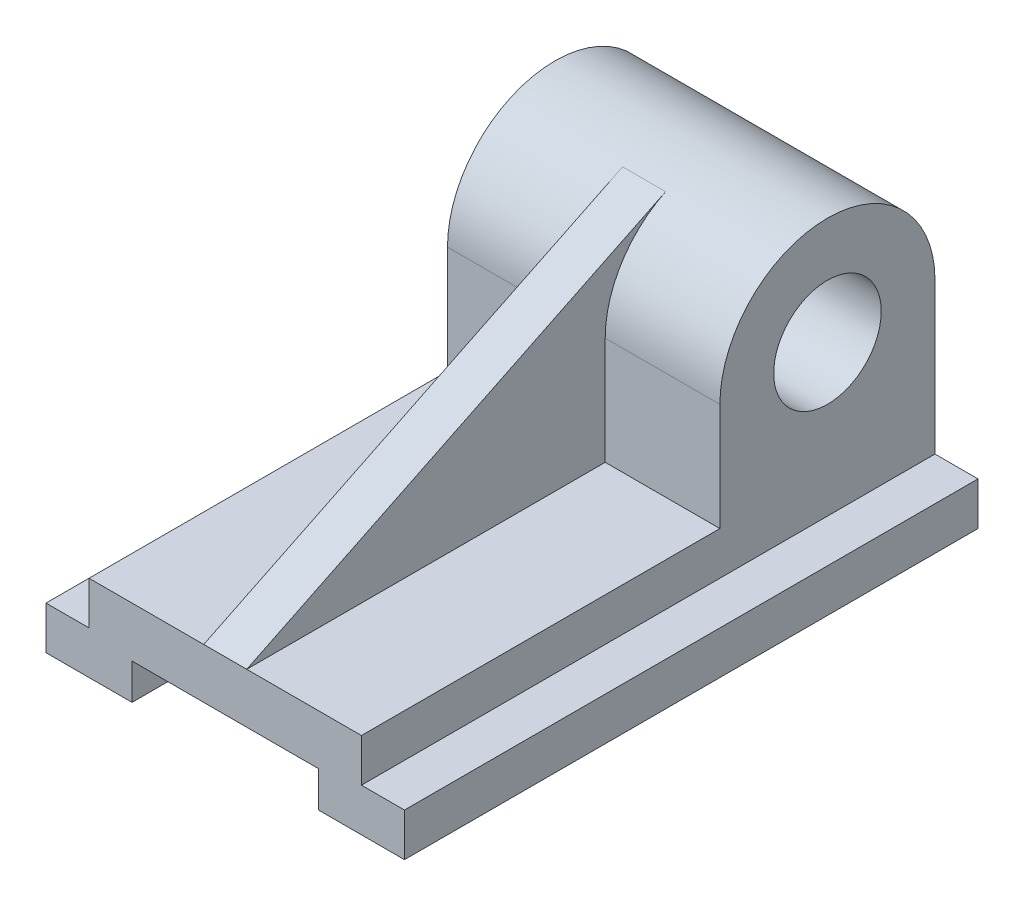
SolidWorks part; units mm, degrees
ref_plane "Front Plane" through (0, 0, 0) normal (0, 0, 1) x (1, 0, 0)
ref_plane "Top Plane" through (0, 0, 0) normal (0, 1, 0) x (1, 0, 0)
ref_plane "Right Plane" through (0, 0, 0) normal (1, 0, 0) x (0, 0, -1)
sketch "Sketch1" plane through (0, 0, 0) normal (0, 0, 1) x (1, 0, 0)
  line L1 (-50, 12) -> (50, 12)
  line L2 (-50, 12) -> (-50, -12)
  line L3 (-50, -12) -> (50, -12)
  line L4 (50, 12) -> (50, -12)
  line L5 (-50, 12) -> (50, -12) construction
  line L6 (-50, -12) -> (50, 12) construction
  point P0 (0, 0)
  dimension "D1" = 100
  dimension "D2" = 24
extrude "Boss-Extrude1" add sketch "Sketch1" along normal blind 160
sketch "Sketch2" plane through (0, 0, 160) normal (0, 0, 1) x (1, 0, 0)
  line L0 (-50, -12) -> (50, -12) construction
  line L1 (-26, -12) -> (26, -12)
  line L2 (-26, -12) -> (-26, -2)
  line L3 (-26, -2) -> (26, -2)
  line L4 (26, -12) -> (26, -2)
  line L6 (50, -12) -> (50, 12) construction
  dimension "D1" = 10
  dimension "D2" = 52
  dimension "D3" = 24
extrude "Cut-Extrude1" cut sketch "Sketch2" against normal through all
sketch "Sketch3" plane through (0, 0, 160) normal (0, 0, 1) x (1, 0, 0)
  line L1 (50, 12) -> (38, 12)
  line L2 (50, 12) -> (50, 0)
  line L3 (50, 0) -> (38, 0)
  line L4 (38, 12) -> (38, 0)
  dimension "D1" = 12
  dimension "D2" = 12
extrude "Cut-Extrude2" cut sketch "Sketch3" against normal through all contours L4 L3 L2 L1
mirror "Mirror1" about plane through (0, 0, 0) normal (1, 0, 0) of "Cut-Extrude2"
sketch "Sketch4" plane through (0, 12, 0) normal (0, 1, 0) x (1, 0, 0)
  line L0 (38, 0) -> (38, -160) construction
  line L1 (-38, 0) -> (38, 0)
  line L2 (-38, 0) -> (-38, -60)
  line L3 (-38, -60) -> (38, -60)
  line L4 (38, 0) -> (38, -60)
  dimension "D1" = 60
extrude "Boss-Extrude3" add sketch "Sketch4" along normal blind 60 contours L3 L4 L1 L2
fillet "Fillet2" 2 edges at (0, 72, 60) (0, 72, 0) type full round first side face at (0, 42, 60) second side face at (0, 7.6667, 0) middle face at (0, 72, 30)
sketch "Sketch6" plane through (38, 0, 0) normal (1, 0, 0) x (0, 0, -1)
  circle A0 centre (-30, 42) radius 15
  dimension "D1" = 30
extrude "Cut-Extrude3" cut sketch "Sketch6" against normal through all
sketch "Sketch9" plane through (0, 0, 0) normal (1, 0, 0) x (0, 0, -1)
  line L0 (-160, 12) -> (-43.1461, 68.9663)
  arc A0 (0, 42) -> (-60, 42) centre (-30, 42) ccw construction
rib "Rib3" sketch "Sketch9" sketch "Sketch9" thickness 12 extrusion direction parallel to sketch draft on no parameters "D1"=12
